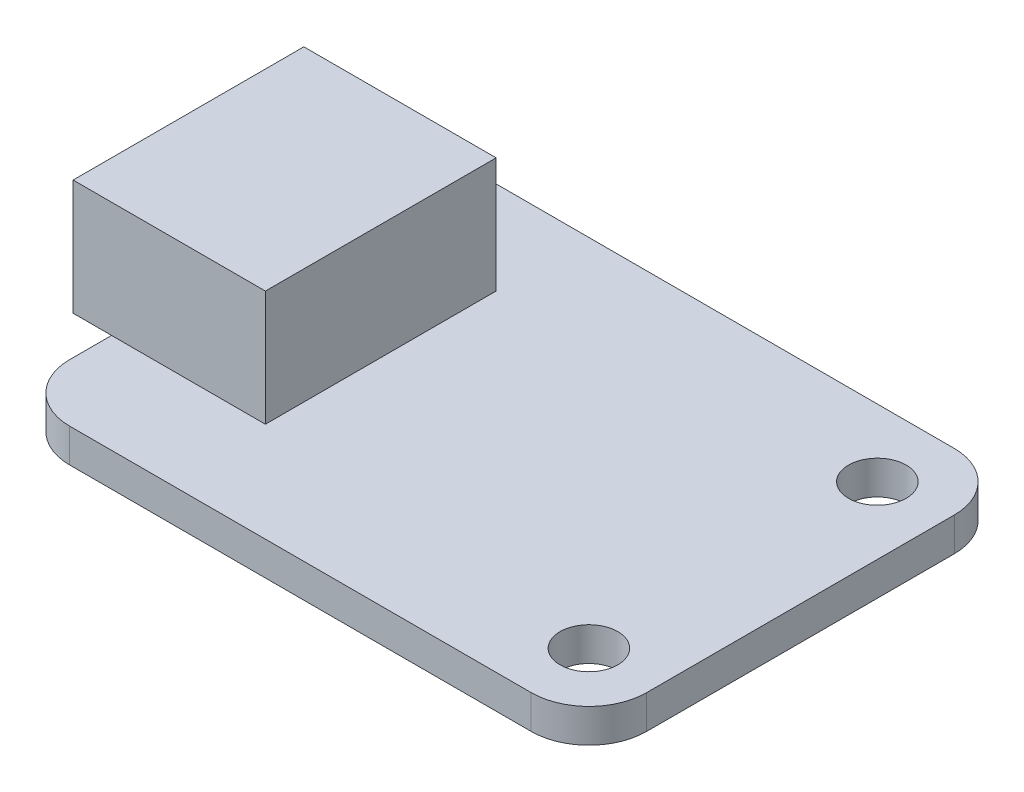
SolidWorks part; units mm, degrees
ref_plane "Front" through (0, 0, 0) normal (0, 0, 1) x (1, 0, 0)
ref_plane "Top" through (0, 0, 0) normal (0, 1, 0) x (1, 0, 0)
ref_plane "Side" through (0, 0, 0) normal (1, 0, 0) x (0, 0, -1)
ref_axis "X_Axis" through (-20.1896, 0, 0) along (1, 0, 0)
ref_axis "Y_Axis" through (0, -14.8261, 0) along (0, 1, 0)
ref_axis "Z_Axis" through (0, 0, -19.842) along (0, 0, 1)
sketch "Sketch1" plane through (0, 0, 0) normal (0, 1, 0) x (1, 0, 0)
  line L0 (15, 0) -> (-15, 0) construction
  line L1 (12, 11) -> (-12, 11)
  line L2 (15, 8) -> (15, -8)
  line L3 (12, -11) -> (-12, -11)
  line L4 (-15, 8) -> (-15, -8)
  line L5 (15, 11) -> (-15, -11) construction
  line L6 (15, -11) -> (-15, 11) construction
  circle A0 centre (11.5, 7.5) radius 1.5
  circle A1 centre (11.5, -7.5) radius 1.5
  arc A2 (-12, -11) -> (-15, -8) centre (-12, -8) cw
  arc A3 (-12, 11) -> (-15, 8) centre (-12, 8) ccw
  arc A4 (15, -8) -> (12, -11) centre (12, -8) cw
  arc A5 (12, 11) -> (15, 8) centre (12, 8) cw
  point P0 (0, 0)
  point P12 (0, 0)
  point P13 (12.357, -7.5)
  dimension "D3" = 3
  dimension "D6" = 3
  dimension "D1" = 30
  dimension "D2" = 22
  dimension "D4" = 15
  dimension "D5" = 3.5
extrude "Boss-Extrude1" add sketch "Sketch1" along normal blind 1.75
sketch "Sketch2" plane through (0, 1.75, 0) normal (0, 1, 0) x (1, 0, 0)
  line L0 (-15, 8) -> (-15, -8) construction
  line L1 (-7, 6.1749) -> (-17, 6.1749)
  line L2 (-7, 6.1749) -> (-7, -5.8251)
  line L3 (-7, -5.8251) -> (-17, -5.8251)
  line L4 (-17, 6.1749) -> (-17, -5.8251)
  line L5 (-7, 6.1749) -> (-17, -5.8251) construction
  line L6 (-7, -5.8251) -> (-17, 6.1749) construction
  point P0 (-12, 0.1749)
  dimension "D1" = 12
  dimension "D2" = 2
  dimension "D3" = 10
extrude "Boss-Extrude2" add sketch "Sketch2" along normal blind 6
